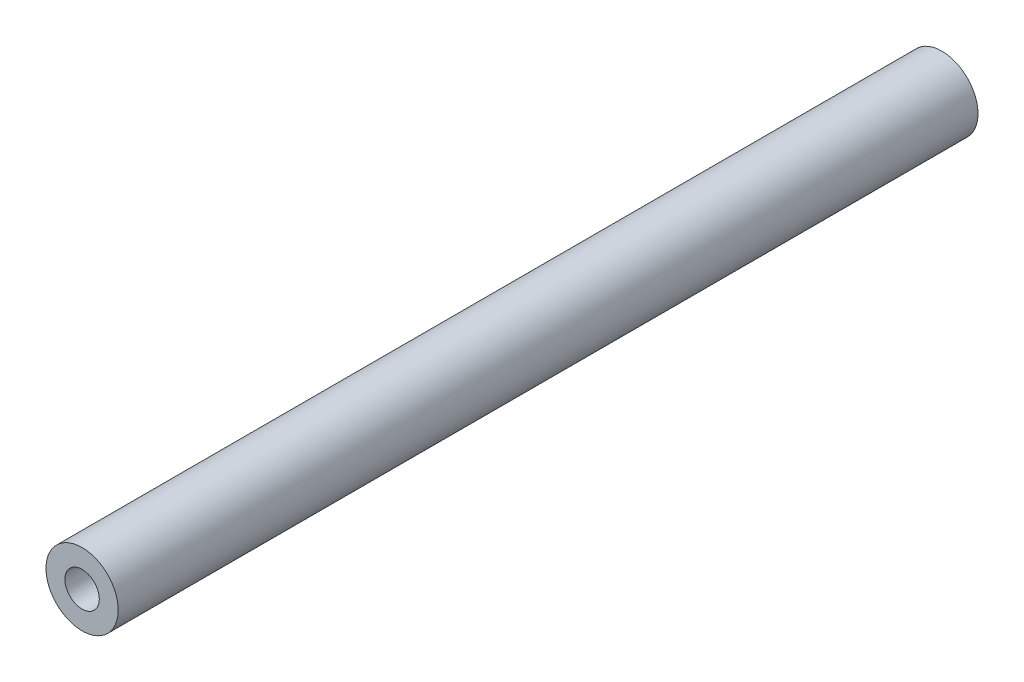
SolidWorks part; units mm, degrees
ref_plane "Front Plane" through (0, 0, 0) normal (0, 0, 1) x (1, 0, 0)
ref_plane "Top Plane" through (0, 0, 0) normal (0, 1, 0) x (1, 0, 0)
ref_plane "Right Plane" through (0, 0, 0) normal (1, 0, 0) x (0, 0, -1)
sketch "Sketch1" plane through (0, 0, 0) normal (1, 0, 0) x (0, 0, -1)
  line L0 (-25.5, 0) -> (25.5, 0) construction
  line L1 (25.5, 0) -> (37.5, 0) construction
  line L2 (-25.5, 0) -> (-37.5, 0) construction
  line L3 (-37.5, -3.15) -> (-37.5, 3.15) construction
  line L4 (37.5, 3.15) -> (37.5, -3.15) construction
  line L5 (0, -3.15) -> (0, 3.15) construction
  line L6 (37.4688, 1.5541) -> (37.9688, 1.5541) construction
  line L7 (37.9688, 1.5541) -> (37.7188, 1.1211) construction
  line L8 (37.7188, 1.1211) -> (37.4688, 1.5541) construction
  line L9 (37.7188, 1.5541) -> (37.7188, 1.5) construction
  line L10 (37.7188, 1.1211) -> (37.7188, 1.1752) construction
  line L11 (37.6875, 1.1752) -> (37.75, 1.1752) construction
  line L12 (37.5, 1.5) -> (37.9375, 1.5) construction
  line L13 (37.7188, 1.5271) -> (37.9531, 1.5271) construction
  line L14 (37.7188, 1.5271) -> (37.4844, 1.5271) construction
  line L15 (37.5, -1.5) -> (37.5, 1.5) construction
  point P4 (0, 0)
  point P10 (-37.5, 0)
  point P13 (37.5, 0)
  point P16 (0, 0)
  point P33 (37.5, 0)
  dimension "Length" = 75
  dimension "Thread Lg" = 12
  dimension "Rod OD" = 6.3
  dimension "Pitch" = 0.5
  dimension "D1" = 0.0625
  dimension "Thread Size" = 3
sketch "Sketch2" plane through (0, 0, 0) normal (1, 0, 0) x (0, 0, -1)
  line L0 (37.5, 1.5) -> (25.5, 1.5)
  line L1 (37.5, 1.5) -> (37.5, 3.15)
  line L2 (37.5, 3.15) -> (-37.5, 3.15)
  line L3 (-37.5, 3.15) -> (-37.5, 1.5)
  line L4 (-37.5, -3.15) -> (-37.5, 3.15) construction
  line L5 (-37.5, 1.5) -> (-25.5, 1.5)
  line L6 (-25.5, 1.5) -> (-25.5, 0)
  line L7 (-25.5, 0) -> (25.5, 0)
  line L8 (25.5, 0) -> (25.5, 1.5)
revolve "Revolve1" add sketch "Sketch2" angle 360 about L2
ref_plane "Plane1" through (0, 0, -37.5) normal (0, 0, 1) x (1, 0, 0)
sketch "Sketch6" plane through (0, 0, 0) normal (1, 0, 0) x (0, 0, -1)
  line L0 (37.5, 1.5) -> (25.5, 1.5) construction
  line L1 (37.5, -1.5) -> (25.5, -1.5) construction
  line L2 (-37.5, 1.5) -> (-25.5, 1.5) construction
  line L3 (-37.5, -1.5) -> (-25.5, -1.5) construction
  line L4 (-25.5, 1.5) -> (-25.5, -1.5) construction
  line L5 (25.5, 1.5) -> (25.5, -1.5) construction
  point P10 (-31.5, -1.5)
sketch "Sketch3" [suppressed] plane through (0, 0, -37.5) normal (0, 0, 1) x (1, 0, 0)
  circle A0 centre (0, 0) radius 1.5
  point P5 (0, 1.5)
curve "Helix/Spiral1" [suppressed] pitch 0.5 height 12.5 turns 25
sketch "Sketch4" [suppressed] plane through (0, 0, 0) normal (1, 0, 0) x (0, 0, -1)
  line L0 (37.4844, 1.5271) -> (37.9531, 1.5271)
  line L1 (37.9531, 1.5271) -> (37.75, 1.1752)
  line L2 (37.75, 1.1752) -> (37.6875, 1.1752)
  line L3 (37.6875, 1.1752) -> (37.4844, 1.5271)
sweep "Sweep1" [suppressed] add profiles "Sketch4" path "Helix/Spiral1"
sketch "Sketch5" [suppressed] plane through (0, 0, -37.5) normal (0, 0, 1) x (1, 0, 0)
  circle A0 centre (0, 0) radius 1.5541
  point P0 (0, 1.5541)
extrude "Cut-Extrude1" [suppressed] cut sketch "Sketch5" along normal through all draft 45 and the other way through all draft 45
pattern_circular "CirPattern1" [suppressed] count 2 over 360 about axis through (0, -3.15, 0) along (0, 1, 0) reverse direction yes of bodies 106
ref_axis "Center Axis 1" through (0, 0, 37.5) along (0, 0, -1)
ref_plane "Contact Plane 1" through (0, 0, 37.5) normal (0, 0, 1) x (1, 0, 0)
ref_plane "Contact Plane 2" through (0, 0, -37.5) normal (0, 0, 1) x (1, 0, 0)
equation "\"D1@Sketch1\"=\"Pitch@Sketch1\"/8"
equation "\"D3@Helix/Spiral1\"=\"Thread Lg@Sketch1\"+\"Pitch@Sketch1\""
equation "\"D4@Helix/Spiral1\"=\"Pitch@Sketch1\""
